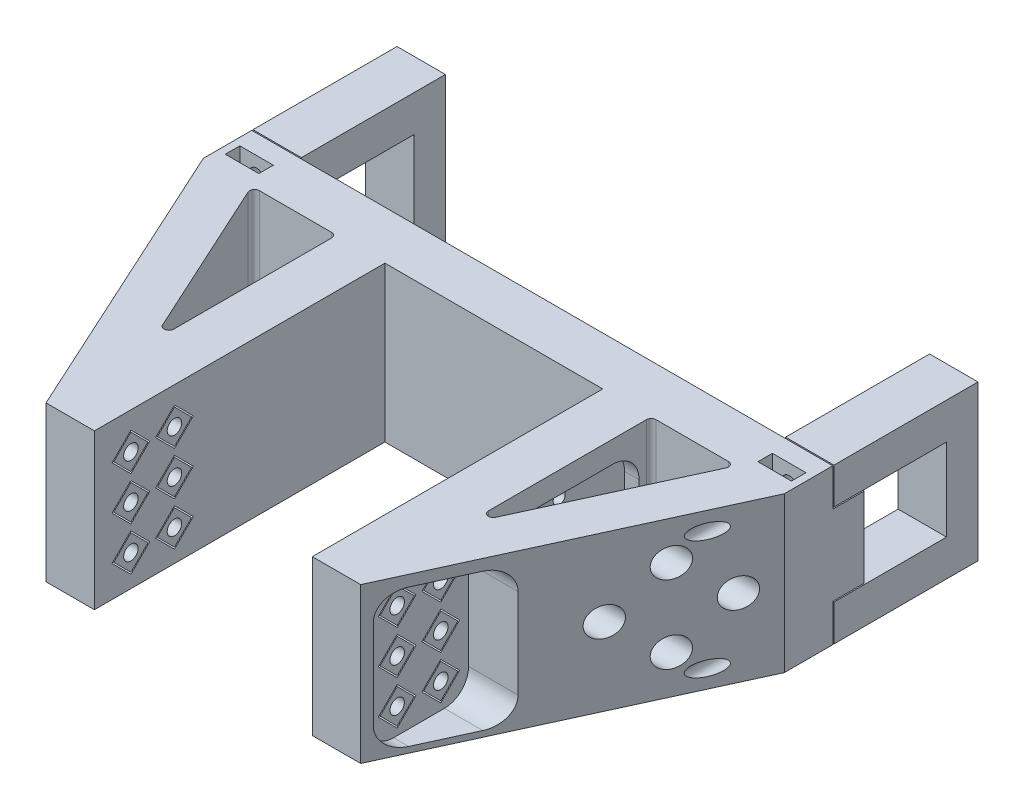
SolidWorks part; units mm, degrees
material "ABS"
ref_plane "Front Plane" through (0, 0, 0) normal (0, 0, 1) x (1, 0, 0)
ref_plane "Top Plane" through (0, 0, 0) normal (0, 1, 0) x (1, 0, 0)
ref_plane "Right Plane" through (0, 0, 0) normal (1, 0, 0) x (0, 0, -1)
ref_axis "X" through (-88.99, 0, 0) along (1, 0, 0)
ref_axis "Y" through (0, 55, 0) along (0, -1, 0)
ref_axis "Z" through (0, 0, -88.99) along (0, 0, 1)
sketch "Sketch1" plane through (0, 0, 0) normal (0, 1, 0) x (1, 0, 0)
  line L0 (-50, 0) -> (50, 0)
  line L1 (50, 0) -> (50, 30)
  line L2 (50, 30) -> (60, 30)
  line L3 (60, 30) -> (60, -10)
  line L4 (60, -10) -> (32.5, -10)
  line L5 (32.5, -10) -> (32.5, -70)
  line L6 (32.5, -70) -> (22.5, -70)
  line L7 (22.5, -70) -> (22.5, -10)
  line L8 (22.5, -10) -> (-22.5, -10)
  line L9 (0, 0) -> (0, -10) construction
  line L10 (60, -10) -> (32.5, -70)
  line L11 (32.5, -48.1818) -> (50, -10)
  line L12 (-32.5, -48.1818) -> (-50, -10)
  line L13 (-60, -10) -> (-32.5, -70)
  line L14 (-22.5, -70) -> (-22.5, -10)
  line L15 (-32.5, -70) -> (-22.5, -70)
  line L16 (-32.5, -10) -> (-32.5, -70)
  line L17 (-60, -10) -> (-32.5, -10)
  line L18 (-60, 30) -> (-60, -10)
  line L19 (-50, 30) -> (-60, 30)
  line L20 (-50, 0) -> (-50, 30)
  dimension "D1" = 50
  dimension "D2" = 60
  dimension "D3" = 10
  dimension "D4" = 10
  dimension "D5" = 10
  dimension "D6" = 30
  dimension "D7" = 120
  dimension "D8" = 100
  dimension "D9" = 45
extrude "Main Extrude" add sketch "Sketch1" along normal mid plane 32 contours L0 L9 L8 L7 L6 L5 L4 L3 L2 L1 | L9 L0 L20 L19 L18 L17 L16 L15 L14 L8 | L11 L5 L10 L4 | L17 L13 L16 L12 region at (-25, 0, 1.1662) region at (25, 0, 1.1662) region at (-43.9352, 0, 34.9495) region at (43.9352, 0, 34.9495)
sketch "Sketch2" plane through (0, 0, 0) normal (1, 0, 0) x (0, 0, -1)
  line L0 (0, 0) -> (15, 0) construction
  line L1 (6.5, 8.5) -> (23.5, 8.5)
  line L2 (6.5, 8.5) -> (6.5, -8.5)
  line L3 (6.5, -8.5) -> (23.5, -8.5)
  line L4 (23.5, 8.5) -> (23.5, -8.5)
  line L5 (6.5, 8.5) -> (23.5, -8.5) construction
  line L6 (6.5, -8.5) -> (23.5, 8.5) construction
  point P0 (15, 0)
  dimension "D1" = 17
  dimension "D2" = 15
extrude "Drive Motor Cutout" cut sketch "Sketch2" against normal through all both and the other way through all
fillet "Sharp Edge Removal" radius 1 6 edges at (32.5, 0, 48.1818) (50, 0, 10) (32.5, 0, 10) (-32.5, 0, 48.1818) (-50, 0, 10) (-32.5, 0, 10)
sketch3d "Component Placement"
  line L0 (0, 0, 0) -> (0, 0, 10) construction
  line L1 (0, 0, 10) -> (0, 0, 26) construction
  line L2 (0, 0, 26) -> (22.5, 0, 26) construction
  dimension "D1" = 16
sketch "Weapon Motor Mount Holes" plane through (32.5, 0, 0) normal (1, 0, 0) x (0, 0, -1)
  line L0 (-34, -11.5) -> (-18, -11.5)
  line L1 (-12.5, -6) -> (-12.5, 6)
  line L2 (-18, 11.5) -> (-34, 11.5)
  line L3 (-39.5, 6) -> (-39.5, -6)
  line L4 (-39, 6) -> (-39, -6)
  line L5 (-34, -11) -> (-18, -11)
  line L6 (-13, -6) -> (-13, 6)
  line L7 (-18, 11) -> (-34, 11)
  line L8 (-39, 6) -> (-39, -6) construction
  line L9 (-34, -11) -> (-18, -11) construction
  line L10 (-13, -6) -> (-13, 6) construction
  line L11 (-18, 11) -> (-34, 11) construction
  circle A0 centre (-16.5, 0) radius 1.25 construction
  circle A1 centre (-35.5, 0) radius 1.25 construction
  circle A2 centre (-26, 8) radius 1.25 construction
  circle A3 centre (-26, -8) radius 1.25 construction
  circle A4 centre (-16.5, 0) radius 1.25
  circle A5 centre (-35.5, 0) radius 1.25
  circle A6 centre (-26, 8) radius 1.25
  circle A7 centre (-26, -8) radius 1.25
  circle A8 centre (-26, 8) radius 3
  circle A9 centre (-16.5, 0) radius 3
  circle A10 centre (-26, -8) radius 3
  circle A11 centre (-35.5, 0) radius 3
  arc A12 (-39.5, -6) -> (-34, -11.5) centre (-34, -6) ccw
  arc A13 (-18, -11.5) -> (-12.5, -6) centre (-18, -6) ccw
  arc A14 (-12.5, 6) -> (-18, 11.5) centre (-18, 6) ccw
  arc A15 (-34, 11.5) -> (-39.5, 6) centre (-34, 6) ccw
  arc A16 (-39, -6) -> (-34, -11) centre (-34, -6) ccw
  arc A17 (-18, -11) -> (-13, -6) centre (-18, -6) ccw
  arc A18 (-13, 6) -> (-18, 11) centre (-18, 6) ccw
  arc A19 (-34, 11) -> (-39, 6) centre (-34, 6) ccw
  arc A20 (-39, -6) -> (-34, -11) centre (-34, -6) ccw construction
  arc A21 (-18, -11) -> (-13, -6) centre (-18, -6) ccw construction
  arc A22 (-13, 6) -> (-18, 11) centre (-18, 6) ccw construction
  arc A23 (-34, 11) -> (-39, 6) centre (-34, 6) ccw construction
  dimension "D1" = 6
  dimension "D2" = 0
  dimension "D3" = 0.5
extrude "Cut-Extrude1" cut sketch "Weapon Motor Mount Holes" against normal up to surface (10 mm away) contours A5 | A6 | A4 | A7 region at (32.5, 0, 16.5) region at (32.5, 0, 35.5) region at (32.5, 8, 26) region at (32.5, -8, 26) up to face at (22.5, 0, 40)
extrude "Cut-Extrude2" cut sketch "Weapon Motor Mount Holes<3>" along normal through all contours A9 | A8 | A11 | A10
sketch "Weapon Motor Mount Holes<3>" plane through (32.5, 0, 0) normal (1, 0, 0) x (0, 0, -1) same geometry as "Weapon Motor Mount Holes"
extrude "Cut-Extrude3" cut sketch "Weapon Motor Mount Holes<4>" against normal blind 3 contours A15 L3 A12 L0 A13 L1 A14 L2
sketch "Weapon Motor Mount Holes<4>" plane through (32.5, 0, 0) normal (1, 0, 0) x (0, 0, -1) same geometry as "Weapon Motor Mount Holes"
sketch "Sketch4" plane through (0, 0, 0) normal (1, 0, 0) x (0, 0, -1)
  line L0 (0, 16) -> (0, -16) construction
  line L1 (0, 16) -> (0, -16)
  line L2 (6.5, -8.5) -> (6.5, 8.5) construction
  line L3 (6.5, -8.5) -> (6.5, 8.5)
  line L4 (6.5, 8.5) -> (0, 8.5)
  line L5 (6.5, -8.5) -> (0, -8.5)
  line L6 (6.5, -8.5) -> (6.5, -8.25)
  line L7 (6.5, -8.25) -> (0.25, -8.25)
  line L8 (6.5, 8.5) -> (6.5, 8.25)
  line L9 (6.5, 8.25) -> (0.25, 8.25)
  line L10 (0, 16) -> (0.25, 16)
  line L11 (0.25, 16) -> (0.25, 8.25)
  line L12 (0, -16) -> (0.25, -16)
  line L13 (0.25, -16) -> (0.25, -8.25)
  line L14 (0.25, 8.25) -> (0, 8.25)
  line L16 (0.25, -8.25) -> (0, -8.25)
  dimension "D1" = 0.25
extrude "Cut-Extrude4" cut sketch "Sketch4" against normal through all both and the other way through all contours L11 L10 L1 L4 L8 L9 | L14 L11 L4 L1 | L4 L11 L9 L3 | L12 L13 L5 L1 | L13 L16 L1 L5 | L13 L5 L3 L7 region at (0, 12.25, -0.125) region at (0, 8.375, -0.125) region at (0, 8.375, -3.375) region at (0, -8.375, -0.125) region at (0, -12.25, -0.125) region at (0, -8.375, -3.375)
sketch "Sketch5" plane through (0, 0, -0.25) normal (0, 0, 1) x (1, 0, 0)
  line L0 (55, 16) -> (55, 8.5) construction
  line L1 (55, -8.5) -> (55, -16) construction
  line L4 (50, 8.5) -> (60, 8.5)
  line L5 (60, 8.5) -> (60, 16)
  line L6 (60, 16) -> (50, 16)
  line L7 (50, 16) -> (50, 8.5)
  line L8 (50, 8.5) -> (60, 8.5)
  line L9 (60, 8.5) -> (60, 16)
  line L10 (60, 16) -> (50, 16)
  line L11 (50, 16) -> (50, 8.5)
  line L12 (50, -8.5) -> (50, -16)
  line L13 (50, -16) -> (60, -16)
  line L14 (60, -16) -> (60, -8.5)
  line L15 (60, -8.5) -> (50, -8.5)
  line L16 (50, -8.5) -> (50, -16)
  line L17 (50, -16) -> (60, -16)
  line L18 (60, -16) -> (60, -8.5)
  line L19 (60, -8.5) -> (50, -8.5)
  circle A0 centre (55, 12.25) radius 1.5
  circle A1 centre (55, -12.25) radius 1.5
  circle A2 centre (55, 12.25) radius 3
  circle A3 centre (55, -12.25) radius 3
  dimension "D3" = 3
  dimension "D4" = 6
  dimension "D1" = 0
  dimension "D2" = 0
extrude "Cut-Extrude5" cut sketch "Sketch5" against normal through all and the other way through all contours A0 | A1 region at (55, 12.25, -0.25) region at (55, -12.25, -0.25)
extrude "Cut-Extrude6" cut sketch "Sketch5<3>" along normal blind 4 from surface contours A2 | A3 starting at face at (56.5, 12.25, -30)
sketch "Sketch5<3>" plane through (0, 0, -0.25) normal (0, 0, 1) x (1, 0, 0) same geometry as "Sketch5"
ref_plane "Plane1" through (0, 0, 4) normal (0, 0, -1) x (-1, 0, 0)
sketch "Sketch6" plane through (0, 0, 4) normal (0, 0, -1) x (-1, 0, 0)
  line L0 (60, 16) -> (-60, 16) construction
  line L1 (-58.4641, 12.25) -> (-56.7321, 9.25)
  line L2 (-56.7321, 9.25) -> (-53.2679, 9.25)
  line L3 (-53.2679, 9.25) -> (-51.5359, 12.25)
  line L4 (-51.5359, 12.25) -> (-53.2679, 15.25) construction
  line L5 (-53.2679, 15.25) -> (-56.7321, 15.25) construction
  line L6 (-56.7321, 15.25) -> (-58.4641, 12.25) construction
  line L7 (-53.2679, -15.25) -> (-51.5359, -12.25) construction
  line L8 (-51.5359, -12.25) -> (-53.2679, -9.25)
  line L9 (-53.2679, -9.25) -> (-56.7321, -9.25)
  line L10 (-56.7321, -9.25) -> (-58.4641, -12.25)
  line L11 (-58.4641, -12.25) -> (-56.7321, -15.25) construction
  line L12 (-56.7321, -15.25) -> (-53.2679, -15.25) construction
  line L13 (60, 16) -> (-60, 16)
  line L14 (60, -16) -> (-60, -16) construction
  line L15 (60, -16) -> (-60, -16)
  line L16 (-58.4641, 12.25) -> (-58.4641, 16)
  line L17 (-51.5359, 12.25) -> (-51.5359, 16)
  line L18 (-58.4641, -12.25) -> (-58.4641, -16)
  line L19 (-51.5359, -12.25) -> (-51.5359, -16)
  circle A0 centre (-55, -12.25) radius 1.5 construction
  circle A1 centre (-55, 12.25) radius 1.5 construction
  circle A2 centre (-55, -12.25) radius 1.5 construction
  circle A3 centre (-55, 12.25) radius 1.5 construction
  circle A4 centre (-55, 12.25) radius 3 construction
  circle A5 centre (-55, -12.25) radius 3 construction
  dimension "D1" = 6
extrude "Cut-Extrude7" cut sketch "Sketch6" against normal blind 3 contours L3 L17 L13 L16 L1 L2 | L19 L8 L9 L10 L18 L15 region at (55, 12.9219, 4) region at (55, -12.9219, 4)
mirror "Mirror1" about plane through (0, 0, 0) normal (1, 0, 0) of "Cut-Extrude7", "Cut-Extrude6", "Cut-Extrude5"
sketch "Sketch7" plane through (0, 0, 0) normal (1, 0, 0) x (0, 0, -1)
  line L0 (-62.4645, 12) -> (-58.9289, 8.4645)
  line L1 (-62.4645, 12) -> (-66, 8.4645)
  line L2 (-58.9289, 8.4645) -> (-62.4645, 4.9289)
  line L3 (-66, 8.4645) -> (-62.4645, 4.9289)
  line L4 (-62.4645, 12) -> (-62.4645, 4.9289) construction
  line L5 (-58.9289, 8.4645) -> (-66, 8.4645) construction
  line L6 (-62.4645, 16) -> (-62.4645, 12) construction
  line L7 (-66, 8.4645) -> (-70, 8.4645) construction
  line L8 (-70, 16) -> (-70, -16) construction
  line L9 (-70, 16) -> (-10, 16) construction
  line L30 (-62.4645, 12.3536) -> (-58.5754, 8.4645)
  line L31 (-58.5754, 8.4645) -> (-62.4645, 4.5754)
  line L32 (-66.3536, 8.4645) -> (-62.4645, 4.5754)
  line L33 (-62.4645, 12.3536) -> (-66.3536, 8.4645)
  circle A0 centre (-62.4645, 8.4645) radius 1.5
  point P1 (-62.4645, 8.4645)
  dimension "D7" = 3
  dimension "D1" = 5
  dimension "D2" = 4
  dimension "D3" = 0.25
extrude "Cut-Extrude8" cut sketch "Sketch7" against normal through all both and the other way through all contours L30 L33 L32 L31 L3 L1 L0 L2 | A0 region at (0, 10.3312, 60.5977) region at (0, 8.4645, 62.4645)
pattern_linear "LPattern1" count 3 spacing 9 along (0, -1, 0) count 2 spacing 9 along (0, 0, -1) of "Cut-Extrude8"
sketch "Sketch8" plane through (0, 0, 0) normal (1, 0, 0) x (0, 0, -1)
  line L0 (-58.9289, -0.5355) -> (-57, -0.5355) construction
  line L1 (-68.2145, -14.7855) -> (-47.7145, -14.7855)
  line L2 (-68.2145, -14.7855) -> (-68.2145, 13.7145)
  line L3 (-68.2145, 13.7145) -> (-47.7145, 13.7145)
  line L4 (-47.7145, -14.7855) -> (-47.7145, 13.7145)
  line L5 (-68.2145, -14.7855) -> (-47.7145, 13.7145) construction
  line L6 (-68.2145, 13.7145) -> (-47.7145, -14.7855) construction
  point P0 (-57.9645, -0.5355)
  dimension "D1" = 28.5
  dimension "D2" = 20.5
extrude "Cut-Extrude13" cut sketch "Sketch8" against normal through all from surface starting at face at (-32.5, 0, 27.3)
extrude "Cut-Extrude14" cut sketch "Sketch8<2>" along normal through all from surface starting at face at (32.5, 0, 26)
sketch "Sketch8<2>" plane through (0, 0, 0) normal (1, 0, 0) x (0, 0, -1) same geometry as "Sketch8"
fillet "Fillet1" radius 5 8 edges at (-32.9092, -14.7855, 68.2145) (-32.9092, 13.7145, 68.2145) (-37.6071, 13.7145, 47.7145) (-37.6071, -14.7855, 47.7145) (32.9092, 13.7145, 68.2145) (32.9092, -14.7855, 68.2145) (37.6071, -14.7855, 47.7145) (37.6071, 13.7145, 47.7145)
